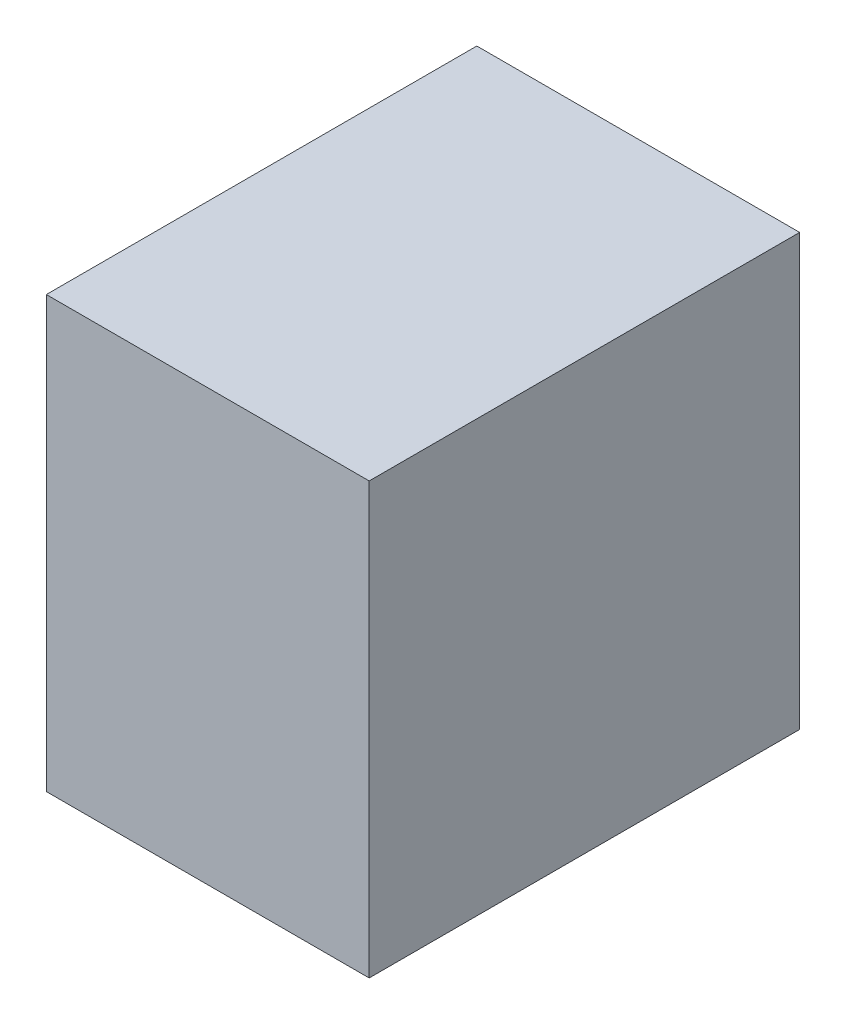
SolidWorks part; units mm, degrees
ref_plane "Front Plane" through (0, 0, 0) normal (0, 0, 1) x (1, 0, 0)
ref_plane "Top Plane" through (0, 0, 0) normal (0, 1, 0) x (1, 0, 0)
ref_plane "Right Plane" through (0, 0, 0) normal (1, 0, 0) x (0, 0, -1)
sketch "Sketch1" plane through (0, 0, 0) normal (1, 0, 0) x (0, 0, -1)
  line L1 (50.8, -50.8) -> (-50.8, -50.8)
  line L2 (50.8, -50.8) -> (50.8, 50.8)
  line L3 (50.8, 50.8) -> (-50.8, 50.8)
  line L4 (-50.8, -50.8) -> (-50.8, 50.8)
  line L5 (50.8, -50.8) -> (-50.8, 50.8) construction
  line L6 (50.8, 50.8) -> (-50.8, -50.8) construction
  point P0 (0, 0)
  dimension "D1" = 101.6
extrude "Boss-Extrude1" add sketch "Sketch1" along normal blind 38.1 and the other way blind 38.1
